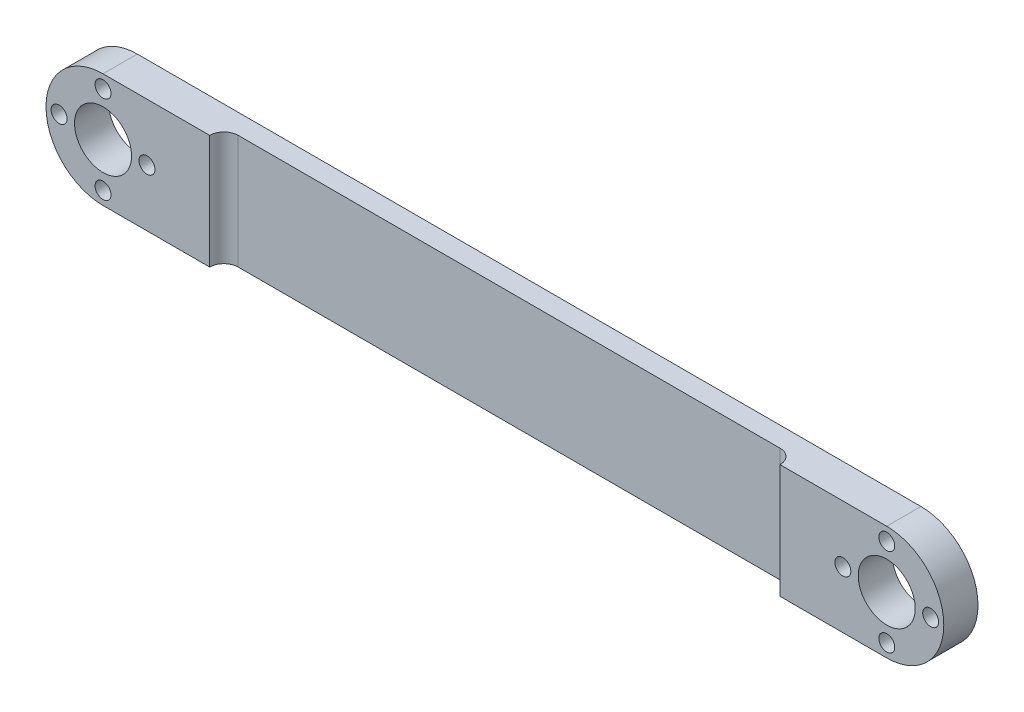
SolidWorks part; units mm, degrees
material "ABS"
ref_plane "Front Plane" through (0, 0, 0) normal (0, 0, 1) x (1, 0, 0)
ref_plane "Top Plane" through (0, 0, 0) normal (0, 1, 0) x (1, 0, 0)
ref_plane "Right Plane" through (0, 0, 0) normal (1, 0, 0) x (0, 0, -1)
sketch "Sketch1" plane through (0, 0, 0) normal (0, 0, 1) x (1, 0, 0)
  line L1 (0, 0) -> (-199.898, 0)
  line L2 (0, 0) -> (0, -25.4)
  line L3 (0, -25.4) -> (-199.898, -25.4)
  line L4 (-199.898, 0) -> (-199.898, -25.4)
  circle A0 centre (-187.198, -12.7) radius 12.7
  circle A1 centre (-12.7, -12.7) radius 12.7
  dimension "D3" = 25.4
  dimension "D5" = 25.4
  dimension "D1" = 199.898
  dimension "D2" = 25.4
  dimension "D4" = 12.7
  dimension "D6" = 12.7
  dimension "D7" = 12.7
  dimension "D8" = 12.7
extrude "Boss-Extrude1" add sketch "Sketch1" along normal blind 7.62 contours A1 L1 A0 L3 | A0 | A1 region at (-99.949, -12.7, 0) region at (-12.7, -12.7, 0) region at (-187.198, -12.7, 0)
sketch "Sketch2" plane through (0, 0, 7.62) normal (0, 0, 1) x (1, 0, 0)
  line L0 (-12.7, 0) -> (-187.198, 0) construction
  circle A0 centre (-12.7, -12.7) radius 6.35
  arc A1 (-12.7, -25.4) -> (-12.7, 0) centre (-12.7, -12.7) ccw construction
  point P7 (0, -12.7)
  dimension "D1" = 12.7
  dimension "D2" = 12.7
  dimension "D3" = 12.7
extrude "Cut-Extrude1" cut sketch "Sketch2" against normal blind 7.62
sketch "Sketch3" plane through (0, 0, 7.62) normal (0, 0, 1) x (1, 0, 0)
  line L0 (-12.7, 0) -> (-187.198, 0) construction
  circle A0 centre (-2.921, -12.7) radius 1.778
  circle A1 centre (-12.7, -12.7) radius 6.35 construction
  dimension "D1" = 3.556
  dimension "D2" = 12.7
  dimension "D3" = 9.779
extrude "Cut-Extrude2" cut sketch "Sketch3" against normal blind 7.62
pattern_circular "CirPattern1" count 4 over 360 about axis through (-12.7, -12.7, 7.62) along (0, 0, 1) of "Cut-Extrude2"
ref_plane "Plane1" through (-99.949, 0, 0) normal (1, 0, 0) x (0, 0, -1)
mirror "Mirror1" about plane through (-99.949, 0, 0) normal (1, 0, 0) of "Cut-Extrude1", "CirPattern1"
sketch "Sketch4" plane through (0, -25.4, 0) normal (0, -1, 0) x (1, 0, 0)
  line L0 (-12.7, 7.62) -> (-187.198, 7.62) construction
  line L1 (-163.449, 7.62) -> (-36.449, 7.62)
  line L2 (-163.449, 7.62) -> (-163.449, 4.445)
  line L3 (-163.449, 4.445) -> (-36.449, 4.445)
  line L4 (-36.449, 7.62) -> (-36.449, 4.445)
  line L5 (-99.949, -4.191) -> (-99.949, 4.191) construction
  dimension "D1" = 127
  dimension "D2" = 63.5
  dimension "D3" = 3.175
extrude "Cut-Extrude3" cut sketch "Sketch4" against normal blind 25.4
fillet "Fillet1" radius 3.175 2 edges at (-36.449, -12.7, 4.445) (-163.449, -12.7, 4.445)
